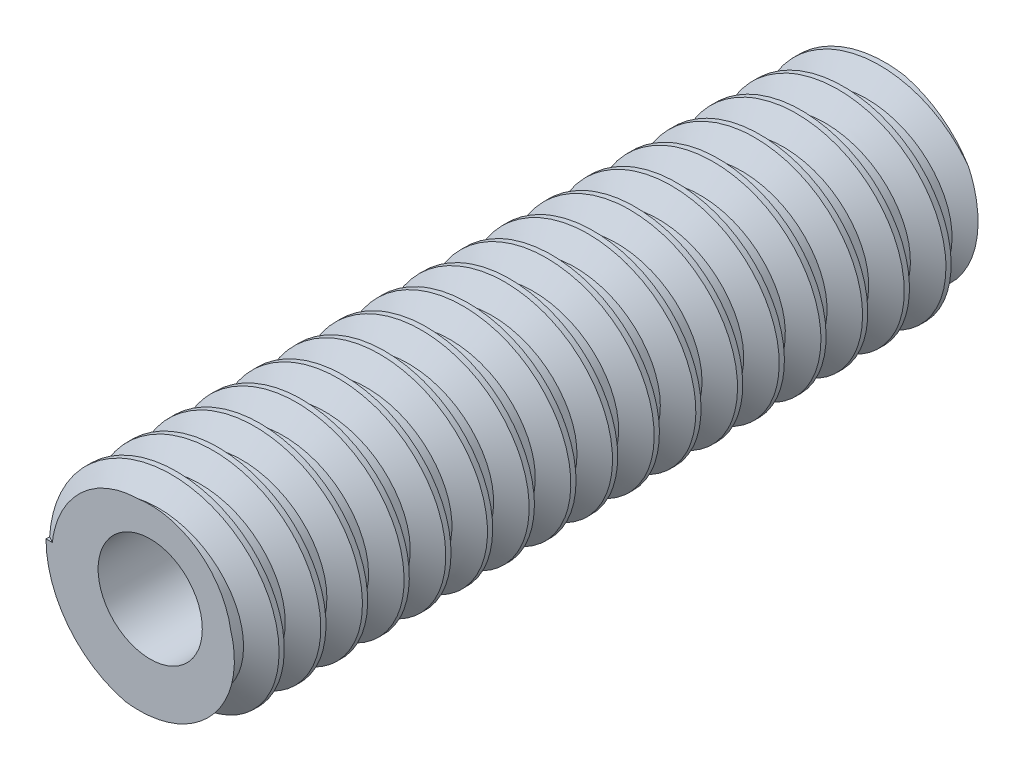
SolidWorks part; units mm, degrees
material "6061-T6 (SS)"
ref_plane "Front Plane" through (0, 0, 0) normal (0, 0, 1) x (1, 0, 0)
ref_plane "Top Plane" through (0, 0, 0) normal (0, 1, 0) x (1, 0, 0)
ref_plane "Right Plane" through (0, 0, 0) normal (1, 0, 0) x (0, 0, -1)
sketch "Sketch1" plane through (0, 0, 0) normal (0, 0, 1) x (1, 0, 0)
  circle A0 centre (0, 0) radius 3.175
  dimension "D1" = 6.35
extrude "Boss-Extrude1" add sketch "Sketch1" along normal blind 22.225
thread "Thread1" pitch 1.27 method cut profile "Thread Profile1" start angle 0, offset 1, length 38.1, pitch 1.27, diameter 6.35
ref_plane "Plane1" through (-3.175, 0, 23.225) normal (0, -1, 0) x (-1, 0, 0)
sketch "Thread Profile1" plane through (-3.175, 0, 23.225) normal (0, -1, 0) x (-1, 0, 0)
  line L0 (0, 0) -> (0, 1.27) construction
  line L11 (0, 0) -> (0, 1.1112)
  line L12 (0, 1.1112) -> (-0.6874, 0.7144)
  line L13 (-0.6874, 0.7144) -> (-0.6874, 0.3969)
  line L15 (-0.6874, 0.3969) -> (0, 0)
  line L17 (-0.6874, 0.5556) -> (0, 0.5556) construction
  point P2 (0, 0)
  dimension "Pitch" = 1.27
  dimension "Profile_Angle" = 60
  dimension "Profile_Land" = 0.3175
  dimension "Profile_Height" = 0.6874
sketch "Sketch5" plane through (0, 0, 22.225) normal (0, 0, 1) x (1, 0, 0)
  circle A0 centre (0, 0) radius 1.5875
  dimension "D1" = 3.175
extrude "Cut-Extrude1" cut sketch "Sketch5" against normal offset from surface (19.05 mm away) 3.175 up to face at (0.1508, 0.401, 0)
